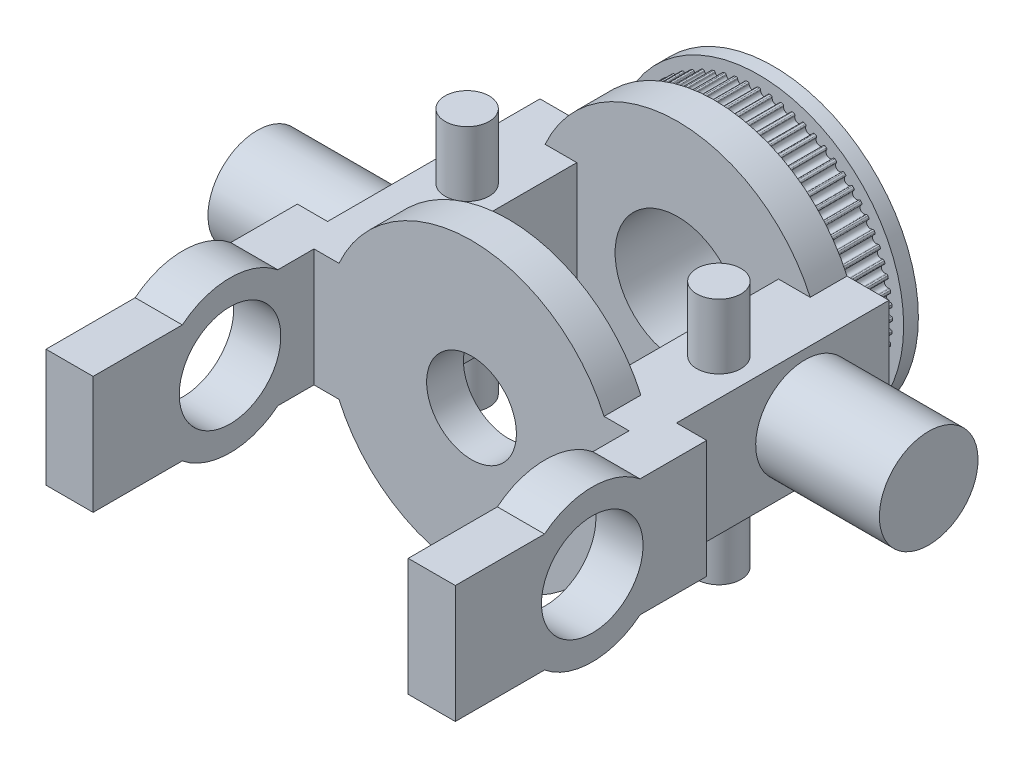
SolidWorks part; units mm, degrees
ref_plane "前视基准面" through (0, 0, 0) normal (0, 0, 1) x (1, 0, 0)
ref_plane "上视基准面" through (0, 0, 0) normal (0, 1, 0) x (1, 0, 0)
ref_plane "右视基准面" through (0, 0, 0) normal (1, 0, 0) x (0, 0, -1)
sketch "Sketch2" plane through (0, 0, 0) normal (0, 0, 1) x (1, 0, 0)
  circle A0 centre (0, 0) radius 90.99
  dimension "D1" = 181.98
extrude "Extrude1" add sketch "Sketch2" along normal blind 30
sketch "Sketch1" plane through (0, 0, 0) normal (0, 0, 1) x (1, 0, 0)
  line L0 (0, 0) -> (0, 91.675) construction
  line L1 (0, 0) -> (-3.9988, 91.5877) construction
  line L2 (-1.3223, 90.2696) -> (-1.3645, 89.7327)
  line L3 (-6.5503, 90.0413) -> (-6.4614, 89.5101)
  circle A0 centre (0, 0) radius 91.675 construction
  arc A1 (-0.5494, 90.9883) -> (-7.3828, 90.69) centre (0, 0) ccw
  arc A2 (-6.4614, 89.5101) -> (-1.3645, 89.7327) centre (-3.9266, 89.9343) ccw
  arc A3 (-0.5494, 90.9883) -> (-1.3223, 90.2696) centre (-0.5447, 90.2084) ccw
  arc A4 (-7.3828, 90.69) -> (-6.5503, 90.0413) centre (-7.3196, 89.9126) cw
  point P4 (91.5877, 3.9988)
  point P5 (90.8907, 11.966)
  point P6 (89.5019, 19.8421)
  point P7 (87.432, 27.5672)
  point P8 (84.6967, 35.0825)
  point P9 (81.3167, 42.3308)
  point P10 (77.3179, 49.2569)
  point P11 (72.7307, 55.8082)
  point P12 (67.5899, 61.9347)
  point P13 (61.9347, 67.5899)
  point P14 (55.8082, 72.7307)
  point P15 (49.2569, 77.3179)
  point P16 (42.3308, 81.3167)
  point P17 (35.0825, 84.6967)
  point P18 (27.5672, 87.432)
  point P19 (19.8421, 89.5019)
  point P20 (11.966, 90.8907)
  point P21 (3.9988, 91.5877)
  point P22 (-3.9988, 91.5877)
  point P23 (-11.966, 90.8907)
  point P24 (-19.8421, 89.5019)
  point P25 (-27.5672, 87.432)
  point P26 (-35.0825, 84.6967)
  point P27 (-42.3308, 81.3167)
  point P28 (-49.2569, 77.3179)
  point P29 (-55.8082, 72.7307)
  point P30 (-61.9347, 67.5899)
  point P31 (-67.5899, 61.9347)
  point P32 (-72.7307, 55.8082)
  point P33 (-77.3179, 49.2569)
  point P34 (-81.3167, 42.3308)
  point P35 (-84.6967, 35.0825)
  point P36 (-87.432, 27.5672)
  point P37 (-89.5019, 19.8421)
  point P38 (-90.8907, 11.966)
  point P39 (-91.5877, 3.9988)
  point P40 (-91.5877, -3.9988)
  point P41 (-90.8907, -11.966)
  point P42 (-89.5019, -19.8421)
  point P43 (-87.432, -27.5672)
  point P44 (-84.6967, -35.0825)
  point P45 (-81.3167, -42.3308)
  point P46 (-77.3179, -49.2569)
  point P47 (-72.7307, -55.8082)
  point P48 (-67.5899, -61.9347)
  point P49 (-61.9347, -67.5899)
  point P50 (-55.8082, -72.7307)
  point P51 (-49.2569, -77.3179)
  point P52 (-42.3308, -81.3167)
  point P53 (-35.0825, -84.6967)
  point P54 (-27.5672, -87.432)
  point P55 (-19.8421, -89.5019)
  point P56 (-11.966, -90.8907)
  point P57 (-3.9988, -91.5877)
  point P58 (3.9988, -91.5877)
  point P59 (11.966, -90.8907)
  point P60 (19.8421, -89.5019)
  point P61 (27.5672, -87.432)
  point P62 (35.0825, -84.6967)
  point P63 (42.3308, -81.3167)
  point P64 (49.2569, -77.3179)
  point P65 (55.8082, -72.7307)
  point P66 (61.9347, -67.5899)
  point P67 (67.5899, -61.9347)
  point P68 (72.7307, -55.8082)
  point P69 (77.3179, -49.2569)
  point P70 (81.3167, -42.3308)
  point P71 (84.6967, -35.0825)
  point P72 (87.432, -27.5672)
  point P73 (89.5019, -19.8421)
  point P74 (90.8907, -11.966)
  point P75 (91.5877, -3.9988)
  dimension "D1" = 183.35
  dimension "D2" = 181.98
  dimension "D3" = 5.14
  dimension "D4" = 3.54
  dimension "D5" = 1.56
  dimension "D6" = 7
extrude "Extrude2" cut sketch "Sketch1" along normal up to surface (30 mm away) up to face at (90.99, 0, 30)
pattern_circular "CirPattern1" count 72 over 360 about axis through (0, 0, 30) along (0, 0, 1) of "Extrude2"
sketch "Sketch3" plane through (0, 0, 30) normal (0, 0, 1) x (1, 0, 0)
  circle A0 centre (0, 0) radius 98.5
  dimension "D1" = 197
extrude "Extrude3" add sketch "Sketch3" along normal blind 25
sketch "Sketch4" plane through (0, 0, 0) normal (0, 0, -1) x (-1, 0, 0)
  circle A0 centre (0, 0) radius 98.5
  dimension "D1" = 197
extrude "Extrude4" add sketch "Sketch4" along normal blind 10
sketch "Sketch7" plane through (0, 0, 55) normal (0, 0, 1) x (1, 0, 0)
  line L0 (0, 0) -> (-98.5, 0) construction
  line L1 (-118.5, 40) -> (-68.5, 40)
  line L2 (-118.5, 40) -> (-118.5, -40)
  line L3 (-118.5, -40) -> (-68.5, -40)
  line L4 (-68.5, 40) -> (-68.5, -40)
  line L5 (0, 0) -> (0, 98.5) construction
  line L6 (118.5, -40) -> (68.5, -40)
  line L7 (68.5, 40) -> (68.5, -40)
  line L8 (118.5, 40) -> (118.5, -40)
  line L9 (118.5, 40) -> (68.5, 40)
  circle A0 centre (0, 0) radius 98.5 construction
  dimension "D1" = 137
  dimension "D2" = 50
  dimension "D3" = 80
extrude "Extrude7" add sketch "Sketch7" along normal blind 140
sketch "Sketch8" plane through (0, 0, 55) normal (0, 0, -1) x (-1, 0, 0)
  line L3 (118.5, 40) -> (90.0125, 40)
  line L4 (90.0125, -40) -> (118.5, -40)
  line L5 (118.5, -40) -> (118.5, 40)
  line L6 (118.5, 40) -> (90.0125, 40)
  line L7 (90.0125, -40) -> (118.5, -40)
  line L8 (118.5, -40) -> (118.5, 40)
  line L9 (-90.0125, 40) -> (-118.5, 40)
  line L10 (-118.5, 40) -> (-118.5, -40)
  line L11 (-118.5, -40) -> (-90.0125, -40)
  line L12 (-90.0125, 40) -> (-118.5, 40)
  line L13 (-118.5, 40) -> (-118.5, -40)
  line L14 (-118.5, -40) -> (-90.0125, -40)
  arc A1 (90.0125, -40) -> (90.0125, 40) centre (0, 0) ccw
  arc A2 (90.0125, -40) -> (90.0125, 40) centre (0, 0) ccw
  arc A3 (-90.0125, 40) -> (-90.0125, -40) centre (0, 0) ccw
  arc A4 (-90.0125, 40) -> (-90.0125, -40) centre (0, 0) ccw
  dimension "D1" = 0
  dimension "D2" = 0
extrude "Extrude8" add sketch "Sketch8" along normal up to surface (25 mm away) up to face at (0, 0, 30)
sketch "Sketch9" plane through (0, 0, 195) normal (0, 0, 1) x (1, 0, 0)
  line L6 (68.5, -40) -> (68.5, 40)
  line L7 (68.5, 40) -> (90.0125, 40)
  line L8 (-90.0125, 40) -> (-68.5, 40)
  line L9 (-68.5, 40) -> (-68.5, -40)
  line L10 (-68.5, -40) -> (-90.0125, -40)
  line L11 (90.0125, -40) -> (68.5, -40)
  line L12 (68.5, -40) -> (68.5, 40)
  line L13 (68.5, 40) -> (90.0125, 40)
  line L14 (-90.0125, 40) -> (-68.5, 40)
  line L15 (-68.5, 40) -> (-68.5, -40)
  line L16 (-68.5, -40) -> (-90.0125, -40)
  line L17 (90.0125, -40) -> (68.5, -40)
  arc A2 (90.0125, 40) -> (-90.0125, 40) centre (0, 0) ccw
  arc A3 (-90.0125, -40) -> (90.0125, -40) centre (0, 0) ccw
  arc A4 (90.0125, 40) -> (-90.0125, 40) centre (0, 0) ccw
  arc A5 (-90.0125, -40) -> (90.0125, -40) centre (0, 0) ccw
  dimension "D1" = 0
extrude "Extrude9" add sketch "Sketch9" against normal blind 25
sketch "Sketch10" plane through (0, 0, -10) normal (0, 0, 1) x (1, 0, 0)
  circle A0 centre (0, 0) radius 42.5
  dimension "D1" = 85
extrude "Extrude10" cut sketch "Sketch10" along normal up to next
sketch "Sketch12" plane through (0, 0, 195) normal (0, 0, 1) x (1, 0, 0)
  line L1 (107, 40) -> (139, 40)
  line L3 (-139, -40) -> (-107, -40)
  line L4 (118.5, 40) -> (90.0125, 40) construction
  line L6 (-107, -40) -> (-107, 40)
  line L8 (107, -40) -> (107, 40)
  line L9 (-107, -40) -> (107, 40) construction
  line L10 (-107, 40) -> (107, -40) construction
  line L11 (-139, -40) -> (-139, 40)
  line L12 (-139, 40) -> (-107, 40)
  line L13 (139, -40) -> (139, 40)
  line L14 (-139, -40) -> (139, 40) construction
  line L15 (-139, 40) -> (139, -40) construction
  line L16 (107, -40) -> (139, -40)
  point P0 (0, 0)
  point P4 (0, 0)
  dimension "D1" = 214
  dimension "D2" = 32
extrude "Extrude12" add sketch "Sketch12" along normal blind 150
sketch "Sketch13" plane through (-118.5, 0, 0) normal (-1, 0, 0) x (0, 0, 1)
  line L0 (195, 0) -> (138, 0) construction
  line L1 (195, 40) -> (195, -40) construction
  circle A0 centre (138, 0) radius 33.5
  dimension "D2" = 67
  dimension "D1" = 57
extrude "Extrude13" add sketch "Sketch13" along normal blind 84
sketch "Sketch14" plane through (118.5, 0, 0) normal (1, 0, 0) x (0, 0, -1)
  line L0 (-30, 0) -> (-87, 0) construction
  line L1 (-30, -40) -> (-30, 40) construction
  circle A0 centre (-87, 0) radius 33.5
  dimension "D2" = 67
  dimension "D1" = 57
extrude "Extrude14" add sketch "Sketch14" along normal blind 84
sketch "Sketch16" plane through (-139, 0, 0) normal (-1, 0, 0) x (0, 0, 1)
  line L0 (195, 40) -> (195, -40) construction
  line L1 (219.5616, 40) -> (284.4384, 40)
  line L2 (345, 40) -> (195, 40) construction
  line L3 (284.4384, -40) -> (219.5616, -40)
  line L4 (345, -40) -> (195, -40) construction
  arc A0 (284.4384, 40) -> (219.5616, 40) centre (252, 0) ccw
  arc A1 (219.5616, -40) -> (284.4384, -40) centre (252, 0) ccw
  point P5 (195, 0)
  dimension "D2" = 103
  dimension "D1" = 57
extrude "Extrude16" add sketch "Sketch16" against normal blind 32
mirror "Mirror1" about plane through (0, 0, 0) normal (1, 0, 0) of "Extrude16"
sketch "Sketch17" plane through (-139, 0, 0) normal (-1, 0, 0) x (0, 0, 1)
  circle A0 centre (252, 0) radius 34.5
  dimension "D1" = 69
extrude "Extrude17" cut sketch "Sketch17" against normal through all
sketch "Sketch19" plane through (0, 40, 0) normal (0, 1, 0) x (1, 0, 0)
  line L0 (-118.5, -104.5) -> (-202.5, -104.5) construction
  line L2 (-68.5, -170) -> (-68.5, -55) construction
  line L3 (118.5, -120.5) -> (202.5, -120.5) construction
  line L5 (68.5, -170) -> (68.5, -55) construction
  circle A0 centre (-93.5, -104.5) radius 15
  circle A1 centre (93.5, -120.5) radius 15
  dimension "D2" = 30
  dimension "D1" = 25
  dimension "D3" = 25
extrude "Extrude18" add sketch "Sketch19" along normal blind 44
sketch "Sketch20" plane through (0, 0, 195) normal (0, 0, 1) x (1, 0, 0)
  circle A0 centre (0, 0) radius 30.5
  dimension "D1" = 61
extrude "Extrude19" cut sketch "Sketch20" against normal up to next
sketch "Sketch23" plane through (-118.5, 0, 0) normal (-1, 0, 0) x (0, 0, 1)
  line L1 (195, 40) -> (174.2767, 40)
  line L2 (195, 40) -> (195, -40)
  line L3 (195, -40) -> (174.2767, -40)
  line L5 (195, -40) -> (30, -40) construction
  arc A0 (174.2767, -40) -> (174.2767, 40) centre (138, 0) ccw
  dimension "D1" = 108
extrude "Extrude20" add sketch "Sketch23" along normal up to surface (20.5 mm away) up to face at (-139, 0, 286.5)
sketch "Sketch25" plane through (0, 40, 0) normal (0, 1, 0) x (1, 0, 0)
  line L0 (139, -219.5616) -> (139, -195) construction
  line L1 (118.5, -195) -> (139, -195)
  line L2 (118.5, -195) -> (118.5, -174.2767)
  line L3 (118.5, -174.2767) -> (139, -174.2767)
  line L4 (139, -195) -> (139, -174.2767)
  line L5 (-139, -174.2767) -> (-118.5, -174.2767) construction
extrude "Extrude22" add sketch "Sketch25" against normal up to surface (80 mm away) up to face at (102.1708, -40, 144.0936)
mirror "Mirror2" about plane through (0, 0, 0) normal (0, 1, 0) of "Extrude18"
